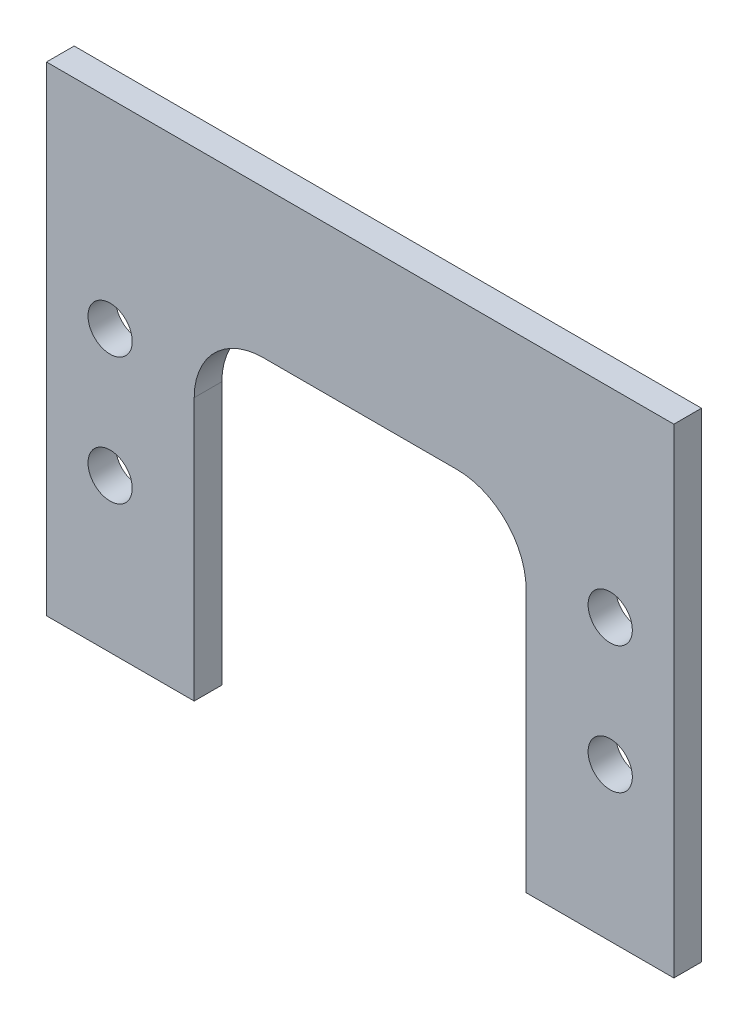
SolidWorks part; units mm, degrees
ref_plane "Front Plane" through (0, 0, 0) normal (0, 0, 1) x (1, 0, 0)
ref_plane "Top Plane" through (0, 0, 0) normal (0, 1, 0) x (1, 0, 0)
ref_plane "Right Plane" through (0, 0, 0) normal (1, 0, 0) x (0, 0, -1)
sketch "Sketch1" plane through (0, 0, 0) normal (0, 0, 1) x (1, 0, 0)
  line L0 (0, 0) -> (0, -25) construction
  line L1 (-5, -17.5) -> (5, -17.5) construction
  line L2 (22.6795, 22.6795) -> (22.6795, -12)
  line L3 (-5, -19) -> (5, -19) construction
  line L4 (-5, -19) -> (-5, -24) construction
  line L5 (-5, -24) -> (5, -24) construction
  line L6 (5, -19) -> (5, -24) construction
  line L7 (22.6795, -12) -> (12, -12)
  line L8 (12, -12) -> (12, 12) construction
  line L9 (12, 12) -> (-12, 12) construction
  line L10 (-12, 12) -> (-12, -12) construction
  line L11 (-12, -12) -> (-22.6795, -12)
  line L12 (-22.6795, -12) -> (-22.6795, 22.6795)
  line L13 (-21.0795, 8.2814) -> (-21.0795, -0.9186) construction
  line L14 (-15.0795, -0.9186) -> (-15.0795, 8.2814) construction
  line L15 (15.0795, -0.9186) -> (15.0795, 8.2814) construction
  line L16 (21.0795, -0.9186) -> (21.0795, 8.2814) construction
  line L17 (-21.0795, 8.2814) -> (-21.0795, -0.9186) construction
  line L18 (-15.0795, -0.9186) -> (-15.0795, 8.2814) construction
  line L19 (15.0795, -0.9186) -> (15.0795, 8.2814) construction
  line L20 (21.0795, -0.9186) -> (21.0795, 8.2814) construction
  line L21 (-22.6795, -5.5186) -> (-22.6795, 19.4814) construction
  line L22 (22.6795, -5.5186) -> (22.6795, 19.4814) construction
  line L23 (-22.6795, -5.5186) -> (-22.6795, 19.4814) construction
  line L24 (22.6795, -5.5186) -> (22.6795, 19.4814) construction
  line L25 (22.6795, -5.5186) -> (-22.6795, -5.5186) construction
  line L26 (-22.6795, 19.4814) -> (22.6795, 19.4814) construction
  line L27 (18.0795, -5.5186) -> (22.6795, -5.5186) construction
  line L28 (22.6795, 19.4814) -> (11.4, 19.4814) construction
  line L29 (-22.6795, 22.6795) -> (22.6795, 22.6795)
  line L30 (10, -12) -> (-10, -12) construction
  line L31 (10, -12) -> (10, 4) construction
  line L32 (10, 4) -> (-10, 4) construction
  line L33 (-10, -12) -> (-10, 4) construction
  line L34 (12, -12) -> (12, 7)
  line L35 (-12, -12) -> (-12, 7)
  line L36 (7, 12) -> (-7, 12)
  line L37 (12, -12) -> (-12, -12) construction
  line L38 (0, 0) -> (12, 0) construction
  circle A0 centre (0, 0) radius 12 construction
  arc A1 (12, 7) -> (7, 12) centre (7, 7) ccw
  circle A2 centre (18.0795, 8.2814) radius 1.6 construction
  circle A3 centre (0, 0) radius 12.5 construction
  circle A4 centre (18.0795, -0.9186) radius 1.6 construction
  circle A5 centre (-18.0795, -0.9186) radius 1.6 construction
  circle A6 centre (-18.0795, -0.9186) radius 1.6
  circle A7 centre (-18.0795, 8.2814) radius 1.6
  circle A8 centre (18.0795, 8.2814) radius 1.6
  circle A9 centre (18.0795, -0.9186) radius 1.6
  circle A10 centre (0, 0) radius 12.5 construction
  circle A11 centre (-18.0795, 8.2814) radius 1.6 construction
  arc A12 (-21.0795, -0.9186) -> (-15.0795, -0.9186) centre (-18.0795, -0.9186) ccw construction
  arc A13 (-15.0795, 8.2814) -> (-21.0795, 8.2814) centre (-18.0795, 8.2814) ccw construction
  arc A14 (15.0795, -0.9186) -> (21.0795, -0.9186) centre (18.0795, -0.9186) ccw construction
  arc A15 (21.0795, 8.2814) -> (15.0795, 8.2814) centre (18.0795, 8.2814) ccw construction
  arc A16 (-21.0795, -0.9186) -> (-15.0795, -0.9186) centre (-18.0795, -0.9186) ccw construction
  arc A17 (-15.0795, 8.2814) -> (-21.0795, 8.2814) centre (-18.0795, 8.2814) ccw construction
  arc A18 (15.0795, -0.9186) -> (21.0795, -0.9186) centre (18.0795, -0.9186) ccw construction
  arc A19 (21.0795, 8.2814) -> (15.0795, 8.2814) centre (18.0795, 8.2814) ccw construction
  circle A20 centre (0, 0) radius 22.6795 construction
  arc A21 (-12, 7) -> (-7, 12) centre (-7, 7) cw
  dimension "D2" = 5
  dimension "D1" = 2
  dimension "D3" = 5
  dimension "D4" = 10
extrude "Boss-Extrude1" add sketch "Sketch1" along normal blind 2
